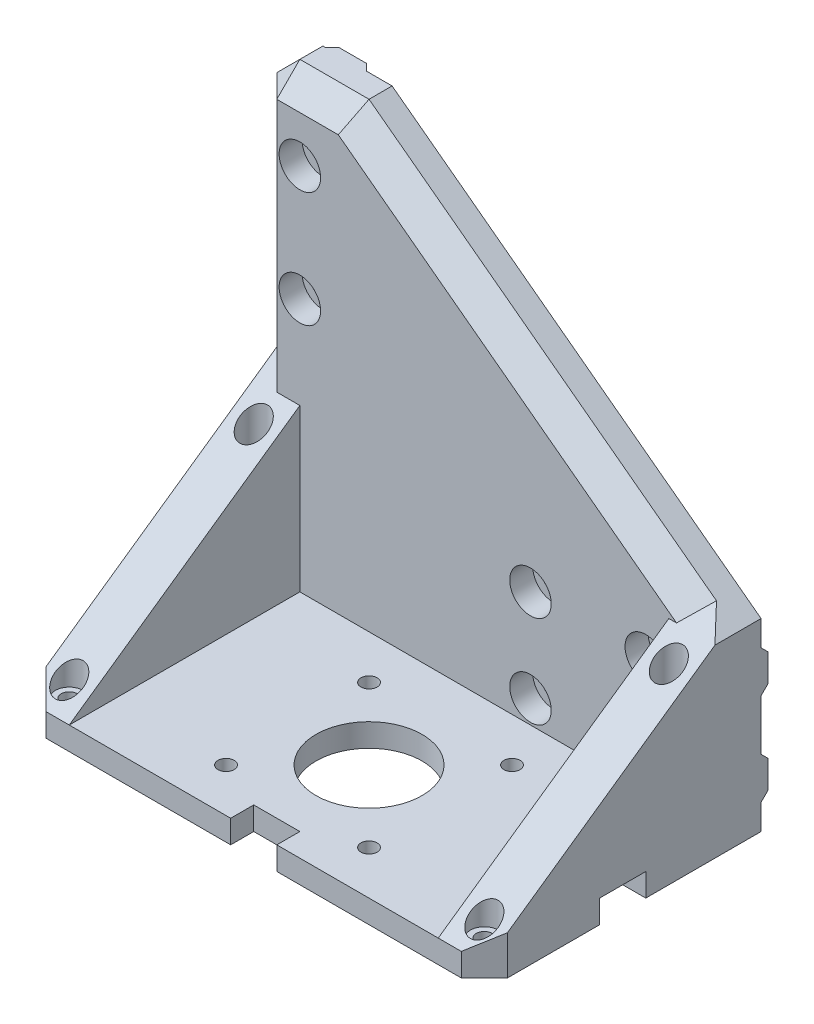
SolidWorks part; units mm, degrees
ref_plane "Płaszczyzna przednia" through (0, 0, 0) normal (0, 0, 1) x (1, 0, 0)
ref_plane "Płaszczyzna górna" through (0, 0, 0) normal (0, 1, 0) x (1, 0, 0)
ref_plane "Płaszczyzna prawa" through (0, 0, 0) normal (1, 0, 0) x (0, 0, -1)
sketch "Sketch1" plane through (0, 0, 0) normal (0, 0, 1) x (1, 0, 0)
  line L0 (0, 0) -> (100, 0)
  line L1 (100, 0) -> (100, 40)
  line L2 (100, 40) -> (20, 100)
  line L3 (20, 100) -> (0, 100)
  line L4 (0, 100) -> (0, 0)
  line L5 (10, 100) -> (10, 0) construction
  line L6 (30, 100) -> (30, 0) construction
  line L8 (100, 30) -> (0, 30) construction
  dimension "D1" = 20
  dimension "D2" = 40
  dimension "D3" = 100
extrude "Boss-Extrude1" add sketch "Sketch1" along normal blind 10
sketch "Sketch2" plane through (0, 0, 0) normal (0, 0, 1) x (1, 0, 0)
  line L5 (10, 100) -> (10, 0) construction
  line L7 (100, 10) -> (0, 10) construction
  line L8 (100, 30) -> (0, 30) construction
  line L9 (0, 0) -> (100, 0) construction
  line L10 (0, 100) -> (0, 0) construction
  line L11 (100, 0) -> (100, 40) construction
  line L12 (0, 100) -> (0, 0) construction
  line L13 (20, 100) -> (0, 100) construction
  line L14 (0, 0) -> (100, 0) construction
  circle A0 centre (10, 85) radius 2.6
  circle A2 centre (10, 60) radius 2.6
  circle A4 centre (85, 30) radius 2.6
  circle A5 centre (85, 10) radius 2.6
  circle A6 centre (60, 10) radius 2.6
  circle A7 centre (60, 30) radius 2.6
  dimension "D9" = 60
  dimension "D1" = 10
  dimension "D2" = 10
  dimension "D4" = 15
  dimension "D6" = 60
  dimension "D7" = 15
  dimension "D8" = 20
extrude "Cut-Extrude1" cut sketch "Sketch2" along normal through all
sketch "Sketch3" plane through (0, 0, 0) normal (0, 0, 1) x (1, 0, 0)
  line L0 (0, 100) -> (0, 0) construction
  line L1 (100, 0) -> (100, 40) construction
  line L2 (100, 25.5) -> (40, 25.5)
  line L3 (100, 25.5) -> (100, 34.5)
  line L4 (100, 34.5) -> (40, 34.5)
  line L5 (40, 25.5) -> (40, 34.5)
  line L6 (20, 100) -> (0, 100) construction
  line L7 (100, 5.5) -> (40, 5.5)
  line L8 (100, 5.5) -> (100, 14.5)
  line L9 (100, 14.5) -> (40, 14.5)
  line L10 (40, 5.5) -> (40, 14.5)
  line L11 (14.5, 100) -> (5.5, 100)
  line L12 (14.5, 100) -> (14.5, 40)
  line L13 (14.5, 40) -> (5.5, 40)
  line L14 (5.5, 100) -> (5.5, 40)
  line L15 (0, 0) -> (100, 0) construction
  circle A0 centre (60, 30) radius 2.6 construction
  circle A1 centre (60, 10) radius 2.6 construction
  circle A3 centre (10, 60) radius 2.6 construction
  dimension "D3" = 4.5
  dimension "D6" = 4.5
  dimension "D10" = 4.5
  dimension "D1" = 40
  dimension "D2" = 40
  dimension "D4" = 9
  dimension "D5" = 9
  dimension "D8" = 9
  dimension "D11" = 40
extrude "Boss-Extrude3" add sketch "Sketch3" against normal blind 1.46 from surface starting at face at (12.6, 85, 0)
extrude "Cut-Extrude2" cut sketch "Sketch2<2>" along normal through all both and the other way through all
sketch "Sketch2<2>" plane through (0, 0, 0) normal (0, 0, 1) x (1, 0, 0) same geometry as "Sketch2"
chamfer "Chamfer1" distance 1.46 angle 45 6 edges at (14.5, 70, -1.46) (5.5, 70, -1.46) (70, 5.5, -1.46) (70, 14.5, -1.46) (70, 25.5, -1.46) (70, 34.5, -1.46)
sketch "Sketch4" plane through (0, 0, 0) normal (0, 0, 1) x (1, 0, 0)
  circle A0 centre (10, 85) radius 4.5
  circle A3 centre (10, 60) radius 4.5
  circle A4 centre (60, 30) radius 4.5
  circle A5 centre (85, 30) radius 4.5
  circle A6 centre (85, 10) radius 4.5
  circle A7 centre (60, 10) radius 4.5
  dimension "D1" = 9
extrude "Cut-Extrude3" cut sketch "Sketch4" against normal blind 5 from surface starting at face at (12.6, 85, 10)
sketch "Sketch5" plane through (0, 0, 0) normal (0, 1, 0) x (1, 0, 0)
  line L0 (100, -35) -> (0, -35) construction
  line L1 (100, -60) -> (0, -60)
  line L2 (100, -60) -> (100, -10)
  line L3 (100, -10) -> (0, -10)
  line L4 (0, -60) -> (0, -10)
  line L5 (50, -10) -> (50, -60) construction
  line L7 (100, -10) -> (100, 0) construction
  line L8 (65.5, -19.5) -> (34.5, -19.5) construction
  line L9 (65.5, -19.5) -> (65.5, -50.5) construction
  line L10 (65.5, -50.5) -> (34.5, -50.5) construction
  line L11 (34.5, -19.5) -> (34.5, -50.5) construction
  line L12 (65.5, -19.5) -> (34.5, -50.5) construction
  line L13 (65.5, -50.5) -> (34.5, -19.5) construction
  line L14 (0, -10) -> (100, -10) construction
  line L15 (0, -10) -> (0, 0) construction
  circle A0 centre (50, -35) radius 11.5
  circle A1 centre (65.5, -50.5) radius 1.75
  circle A2 centre (34.5, -50.5) radius 1.75
  circle A3 centre (34.5, -19.5) radius 1.75
  circle A4 centre (65.5, -19.5) radius 1.75
  point P22 (57.1486, -35)
  point P23 (33.8933, -35)
  dimension "D2" = 23
  dimension "D5" = 3.5
  dimension "D1" = 50
  dimension "D3" = 31
  dimension "D4" = 31
extrude "Boss-Extrude4" add sketch "Sketch5" along normal blind 5
sketch "Sketch8" plane through (0, 0, 0) normal (1, 0, 0) x (0, 0, -1)
  line L0 (-10, 5) -> (-60, 5)
  line L1 (-60, 5) -> (-10, 40)
  line L2 (-10, 40) -> (-10, 5)
  line L3 (-10, 5) -> (-10, 40) construction
  line L4 (-10, 100) -> (-10, 5) construction
extrude "Boss-Extrude5" add sketch "Sketch8" along normal blind 10
extrude "Boss-Extrude6" add sketch "Sketch8<2>" against normal blind 10 from surface starting at face at (100, 17.8571, 9.5829)
sketch "Sketch8<2>" plane through (0, 0, 0) normal (1, 0, 0) x (0, 0, -1) same geometry as "Sketch8"
sketch "Sketch9" plane through (0, 0, 0) normal (0, 1, 0) x (1, 0, 0)
  line L1 (5, -15) -> (95, -15) construction
  line L2 (5, -15) -> (5, -55) construction
  line L3 (5, -55) -> (95, -55) construction
  line L4 (95, -15) -> (95, -55) construction
  line L5 (5, -15) -> (95, -55) construction
  line L6 (5, -55) -> (95, -15) construction
  line L7 (0, 0) -> (100, 0) construction
  line L10 (0, -60) -> (100, -60) construction
  line L11 (0, -60) -> (0, 0) construction
  line L12 (100, -60) -> (100, 0) construction
  circle A0 centre (5, -55) radius 1.75
  circle A1 centre (95, -55) radius 1.75
  circle A2 centre (95, -15) radius 1.75
  circle A3 centre (5, -15) radius 1.75
  point P0 (50, -35)
  dimension "D5" = 3.5
  dimension "D1" = 5
  dimension "D2" = 15
  dimension "D3" = 5
  dimension "D4" = 5
extrude "Cut-Extrude4" cut sketch "Sketch9" along normal through all both and the other way through all
sketch "Sketch10" plane through (0, 0, 0) normal (1, 0, 0) x (0, 0, -1)
  line L0 (-35, 0) -> (-25, 0)
  line L1 (-35, 0) -> (-35, 5)
  line L2 (-25, 0) -> (-25, 5)
  line L3 (-35, 5) -> (-25, 5)
  line L4 (-25, 0) -> (0, 0) construction
  line L6 (-60, 5) -> (-60, 0) construction
  point P6 (-30, 0)
  dimension "D1" = 5
  dimension "D2" = 5
  dimension "D3" = 25
extrude "Cut-Extrude5" cut sketch "Sketch10" along normal blind 5
extrude "Cut-Extrude6" cut sketch "Sketch10<2>" against normal blind 5 from surface starting at face at (100, 18.8462, 9.5508)
sketch "Sketch10<2>" plane through (0, 0, 0) normal (1, 0, 0) x (0, 0, -1) same geometry as "Sketch10"
sketch "Sketch11" plane through (0, 0, 0) normal (0, 0, 1) x (1, 0, 0)
  line L0 (55, 0) -> (45, 0)
  line L1 (55, 0) -> (55, 5)
  line L2 (45, 0) -> (45, 5)
  line L3 (55, 5) -> (45, 5)
  line L4 (0, 0) -> (100, 0) construction
  line L5 (10, 5) -> (90, 5) construction
  line L6 (0, 100) -> (0, 0) construction
  point P8 (50, 0)
  dimension "D1" = 5
  dimension "D2" = 45
extrude "Cut-Extrude7" cut sketch "Sketch11" against normal blind 5 from surface starting at face at (50, 3.3333, 60)
sketch "Sketch12" plane through (0, 0, 0) normal (0, 1, 0) x (1, 0, 0)
  circle A0 centre (5, -15) radius 3
  circle A1 centre (5, -55) radius 3
  circle A2 centre (95, -55) radius 3
  circle A3 centre (95, -15) radius 3
  dimension "D1" = 6
extrude "Cut-Extrude9" cut sketch "Sketch12" against normal blind 95 from surface starting at face at (10, 100, 2.135)
chamfer "Chamfer2" distance 5 angle 45 6 edges at (100, 2.5, 60) (0, 2.5, 60) (0, 100, 5) (0, 70, 10) (10, 100, 10) (60, 70, 10)
